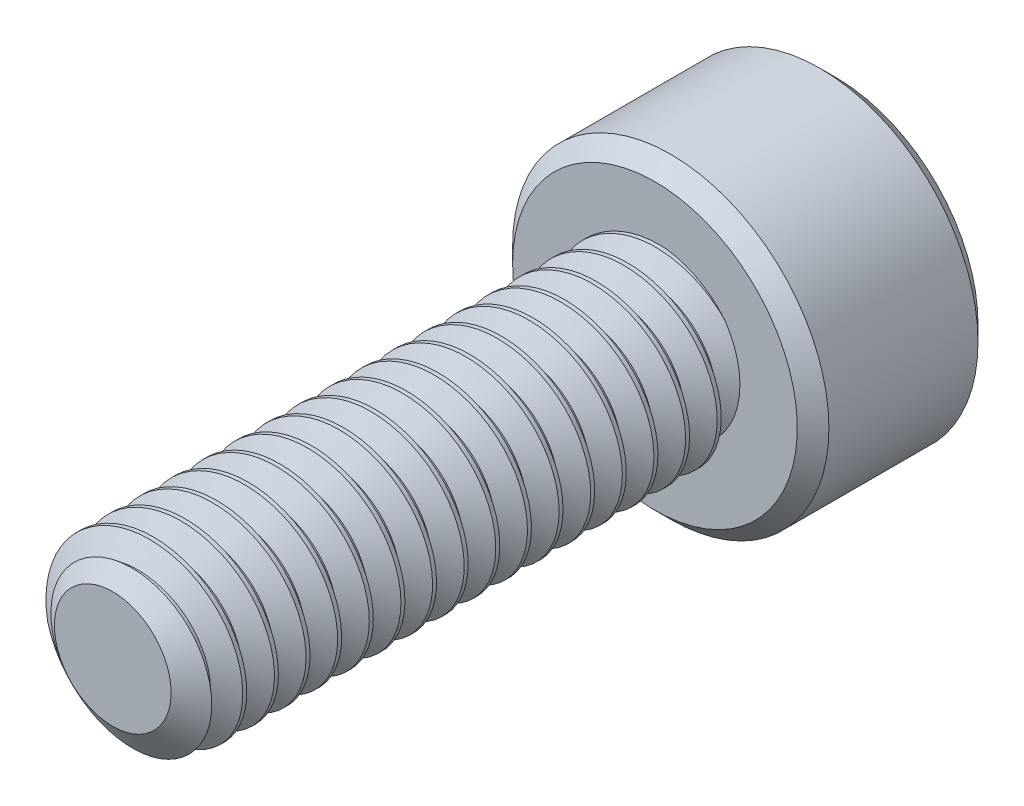
SolidWorks part; units mm, degrees
note: '?' marks a value the reader was unsure of.
other "DetailItem1"
material "Chrome Stainless Steel"
ref_plane "Front Plane" through (0, 0, 0) normal (0, 0, 1) x (1, 0, 0)
ref_plane "Top Plane" through (0, 0, 0) normal (0, 1, 0) x (1, 0, 0)
ref_plane "Right Plane" through (0, 0, 0) normal (1, 0, 0) x (0, 0, -1)
sketch "Sketch1" plane through (0, 0, 0) normal (0, 0, 1) x (1, 0, 0)
  circle A0 centre (0, 0) radius 2
  dimension "OD" = 4
extrude "Extrude1" add sketch "Sketch1" against normal blind 12
sketch "Sketch2" plane through (0, 0, 0) normal (0, 0, 1) x (1, 0, 0)
  circle A0 centre (0, 0) radius 2 construction
  circle A1 centre (0, 0) radius 2
curve "Helix/Spiral1" pitch 0.7 height 12.7 turns 18.1429 parameters "pitch"=0.7
sketch "Sketch3" plane through (0, 0, 0) normal (1, 0, 0) x (0, 0, -1)
  line L0 (-0.6125, 2) -> (-0.35, 1.5453)
  line L1 (-0.35, 1.5453) -> (-0.2625, 1.5453)
  line L2 (-0.2625, 1.5453) -> (0, 2)
  line L3 (-0.6125, 2) -> (0, 2)
  line L4 (-0.3062, 2) -> (-0.3062, 1.5453) construction
  line L5 (-0.4812, 1.7727) -> (-0.1312, 1.7727) construction
  line L6 (0, 2) -> (0, -2) construction
  dimension "D1" = 0.0875
  dimension "D2" = 0.35
  dimension "D3" = 60
sweep "Cut-Sweep1" cut profiles "Sketch3" path "Helix/Spiral1"
sketch "Sketch4" plane through (0, 0, 0) normal (1, 0, 0) x (0, 0, -1)
  line L0 (0.4962, 2) -> (0, 1.2913)
  line L1 (0, 1.2913) -> (0, 2)
  line L2 (0.4962, 2) -> (0, 2)
  line L3 (-0.6125, 2) -> (0, 2) construction
  line L4 (0, 0) -> (7.0209, 0) construction
  dimension "D1" = 55
  dimension "D2" = 0.254
revolve "Cut-Revolve1" cut sketch "Sketch4" angle 360 about L4
sketch "Sketch6" plane through (0, 0, -12) normal (0, 0, -1) x (-1, 0, 0)
  circle A0 centre (0, 0) radius 3.5
  dimension "head dia" = 7
extrude "Extrude2" add sketch "Sketch6" along normal blind 4
sketch "Sketch7" plane through (0, 0, -16) normal (0, 0, -1) x (-1, 0, 0)
  line L1 (0, 1.7321) -> (-1.5, 0.866)
  line L2 (-1.5, 0.866) -> (-1.5, -0.866)
  line L3 (-1.5, -0.866) -> (0, -1.7321)
  line L4 (0, -1.7321) -> (1.5, -0.866)
  line L5 (1.5, -0.866) -> (1.5, 0.866)
  line L6 (1.5, 0.866) -> (0, 1.7321)
  circle A0 centre (0, 0) radius 1.5 construction
  dimension "hex dia" = 3
extrude "Cut-Extrude1" cut sketch "Sketch7" against normal blind 2.25
sketch "Sketch8" plane through (0, 0, -16) normal (0, 0, -1) x (-1, 0, 0)
  circle A0 centre (0, 0) radius 1.7321
extrude "Cut-Extrude2" cut sketch "Sketch8" against normal through all draft 45
chamfer "Chamfer1" distance 0.35 angle 45 2 edges at (-3.5, 0, -16) (-3.5, 0, -12)
sketch "Sketch10" plane through (0, 0, -12) normal (0, 0, 1) x (1, 0, 0)
  circle A1 centre (0, 0) radius 2
  circle A2 centre (0, 0) radius 2
  dimension "D1" = 0
ref_plane "Plane1" through (0, 0, 0) normal (0, 0, 1) x (1, 0, 0)
extrude "partial thread" [suppressed] add sketch "Sketch10" along normal up to surface (10 mm away) separate body
chamfer "Chamfer2" [suppressed] distance 0.08 angle 45
combine bodies "Combine1" [suppressed] operation type? add bodies to combine 107 108
sketch "Sketch9" plane through (0, 0, 0) normal (1, 0, 0) x (0, 0, -1)
  line L0 (0, 2) -> (0, -2) construction
  line L1 (1.75, 2) -> (1.75, -2) construction
  dimension "D1" = 1.75
equation "\"D3@Helix/Spiral1\" = \"screw length@Extrude1\"+\"pitch@Helix/Spiral1\""
equation "\"D1@Sketch3\" = \"pitch@Helix/Spiral1\"*.125"
equation "\"D2@Sketch3\" = \"pitch@Helix/Spiral1\"*.5"
equation "\"D1@Cut-Extrude1\" = \"hex dia@Sketch7\"*.75"
equation "\"D1@Chamfer1\" = \"head dia@Sketch6\"*.05"
equation "\"D1@Sketch9\" = \"pitch@Helix/Spiral1\"*2.5"
equation "\"D1@Chamfer2\"=\"OD@Sketch1\"*.02"
